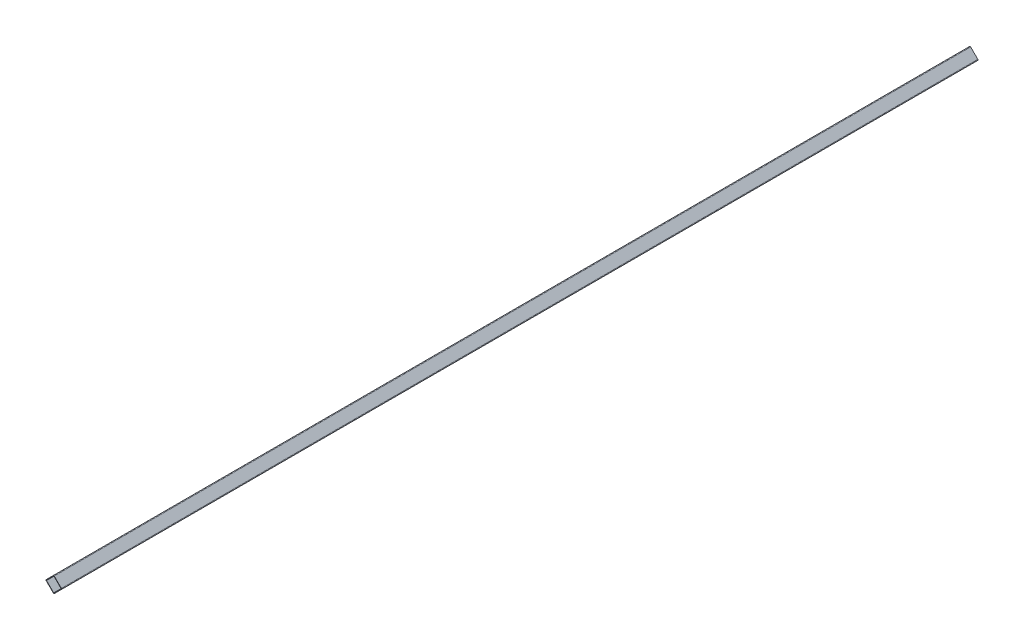
SolidWorks part; units mm, degrees
ref_plane "Front" through (0, 0, 0) normal (0, 0, 1) x (1, 0, 0)
ref_plane "Top" through (0, 0, 0) normal (0, 1, 0) x (1, 0, 0)
ref_plane "Right" through (0, 0, 0) normal (1, 0, 0) x (0, 0, -1)
sketch "inch square tube" plane through (0, 0, 0) normal (0, 0, 1) x (1, 0, 0)
  line L0 (0, 0) -> (-13.4704, -13.4704) construction
  line L1 (25.2437, -1.6971) -> (1.6971, -25.2437)
  line L2 (25.2437, 1.6971) -> (1.6971, 25.2437)
  line L3 (-1.6971, 25.2437) -> (-25.2437, 1.6971)
  line L4 (-1.6971, -25.2437) -> (-25.2437, -1.6971)
  line L5 (0, 0) -> (13.4704, -13.4704) construction
  line L7 (-24.1123, 0.5657) -> (-0.5657, 24.1123)
  line L8 (-24.1123, -0.5657) -> (-0.5657, -24.1123)
  line L9 (0.5657, -24.1123) -> (24.1123, -0.5657)
  line L10 (0.5657, 24.1123) -> (24.1123, 0.5657)
  circle A0 centre (0, 0) radius 14.1224 construction
  arc A1 (1.6971, -25.2437) -> (-1.6971, -25.2437) centre (0, -23.5467) cw
  arc A2 (25.2437, -1.6971) -> (25.2437, 1.6971) centre (23.5467, 0) ccw
  arc A3 (1.6971, 25.2437) -> (-1.6971, 25.2437) centre (0, 23.5467) ccw
  arc A4 (-25.2437, 1.6971) -> (-25.2437, -1.6971) centre (-23.5467, 0) ccw
  arc A5 (-0.5657, 24.1123) -> (0.5657, 24.1123) centre (0, 23.5467) cw
  arc A6 (24.1123, -0.5657) -> (24.1123, 0.5657) centre (23.5467, 0) ccw
  arc A7 (-0.5657, -24.1123) -> (0.5657, -24.1123) centre (0, -23.5467) ccw
  arc A8 (-24.1123, 0.5657) -> (-24.1123, -0.5657) centre (-23.5467, 0) ccw
  point P0 (0, 0)
  point P1 (-12.339, -12.339)
  point P4 (12.339, -12.339)
  point P12 (13.4704, 13.4704)
  point P13 (-13.4704, -13.4704)
  point P14 (-13.4704, 13.4704)
  point P35 (0, -26.9408)
  point P36 (13.4704, -13.4704)
  point P37 (-26.9408, 0)
  point P38 (0, 26.9408)
  point P39 (26.9408, 0)
  point P40 (0, 0)
  point P41 (0, 0)
  point P42 (0, 0)
  dimension "D2" = 14.1224
  dimension "D4" = 2.4
  dimension "D5" = 0.8
  dimension "D3" = 1.6
  dimension "D1" = 38.1
extrude "Boss-Extrude1" add sketch "inch square tube" along normal blind 3048
sketch "Sketch1" plane through (0, 0, 3048) normal (0, 0, 1) x (1, 0, 0)
  line L0 (0, 0) -> (0, 24.3467) construction
  line L1 (0, 0) -> (24.3467, 0) construction
  line L2 (0, 0) -> (-24.3467, 0) construction
  line L3 (0, 0) -> (0, -24.3467) construction
  arc A0 (0.5657, 24.1123) -> (-0.5657, 24.1123) centre (0, 23.5467) ccw construction
  arc A1 (24.1123, -0.5657) -> (24.1123, 0.5657) centre (23.5467, 0) ccw construction
  arc A2 (-24.1123, 0.5657) -> (-24.1123, -0.5657) centre (-23.5467, 0) ccw construction
  arc A3 (-0.5657, -24.1123) -> (0.5657, -24.1123) centre (0, -23.5467) ccw construction
  point P0 (0, 0)
equation "\"D4@inch square tube\" = \"D3@inch square tube\" * 1.5"
equation "\"D5@inch square tube\" = \"D4@inch square tube\" - \"D3@inch square tube\""
equation "\"10feet\"=0.6"
